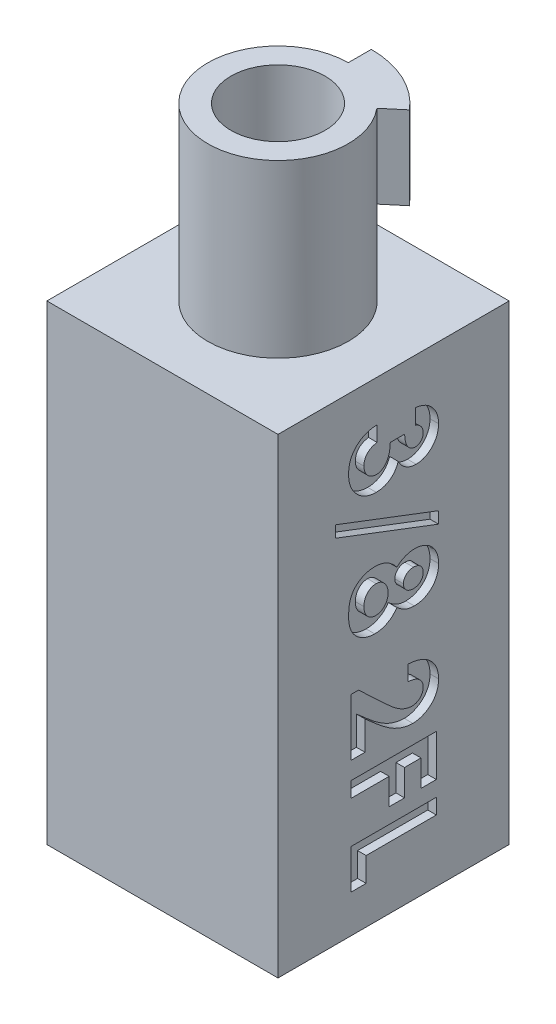
SolidWorks part; units mm, degrees
ref_plane "Front Plane" through (0, 0, 0) normal (0, 0, 1) x (1, 0, 0)
ref_plane "Top Plane" through (0, 0, 0) normal (0, 1, 0) x (1, 0, 0)
ref_plane "Right Plane" through (0, 0, 0) normal (1, 0, 0) x (0, 0, -1)
sketch "Sketch1" plane through (0, 0, 0) normal (0, 1, 0) x (1, 0, 0)
  line L1 (13.5, -13.5) -> (-13.5, -13.5)
  line L2 (13.5, -13.5) -> (13.5, 13.5)
  line L3 (13.5, 13.5) -> (-13.5, 13.5)
  line L4 (-13.5, -13.5) -> (-13.5, 13.5)
  circle A0 centre (0, 0) radius 8.2
  circle A1 centre (0, 0) radius 5.5
  point P6 (0, -13.5)
  point P7 (13.5, 0)
  point P8 (-44.8889, -44.8889)
  point P11 (17.3757, -17.3757)
  dimension "D1" = 11
  dimension "D2" = 16.4
  dimension "D3" = 27
extrude "Boss-Extrude1" add sketch "Sketch1" against normal blind 10 contours A0 A1 | A1 | L4 L1 L2 L3 A0 region at (0, 0, 13.1182) region at (-7.9681, 0, 0) region at (0, 0, 0)
extrude "Boss-Extrude2" add sketch "Sketch1<3>" along normal blind 45 contours A0 A1 | L4 L1 L2 L3 A0 region at (0, 0, 13.1182) region at (-7.9681, 0, 0)
sketch "Sketch1<3>" plane through (0, 0, 0) normal (0, 1, 0) x (1, 0, 0) same geometry as "Sketch1"
extrude "Boss-Extrude3" add sketch "Sketch1<4>" along normal blind 65 contours A0 A1 region at (-7.9681, 0, 0)
sketch "Sketch1<4>" plane through (0, 0, 0) normal (0, 1, 0) x (1, 0, 0) same geometry as "Sketch1"
sketch "Sketch2" plane through (0, 65, 0) normal (0, 1, 0) x (1, 0, 0)
  line L0 (0, 8.2) -> (0, 10.9)
  line L1 (6.2816, 5.2709) -> (8.3499, 7.0064)
  circle A0 centre (0, 0) radius 8.2 construction
  circle A1 centre (0, 0) radius 8.2 construction
  arc A2 (6.2816, 5.2709) -> (0, 8.2) centre (0, 0) ccw
  arc A5 (8.3499, 7.0064) -> (0, 10.9) centre (0, 0) ccw
  point P12 (8.1267, 8.0873)
  dimension "D1" = 50
  dimension "D2" = 2.7
extrude "Boss-Extrude4" add sketch "Sketch2" against normal blind 9.7
sketch "Sketch3" plane through (13.5, 0, 0) normal (1, 0, 0) x (0, 0, -1)
  line L0 (-5, 45) -> (-5, -10) construction
  text T0 "3/8 2FL" font "Century Gothic" height 10
  point P3 (0, 0)
  point P4 (-3.0016, 0.6305)
  point P5 (0, 0)
  dimension "D1" = 5
extrude "Cut-Extrude1" cut sketch "Sketch3" against normal blind 1
equation "\"D2@Sketch1\"=\"D1@Sketch1\"+6-.6mm"
equation "\"D3@Sketch1\"=\"D2@Sketch1\"+10+.6mm"
